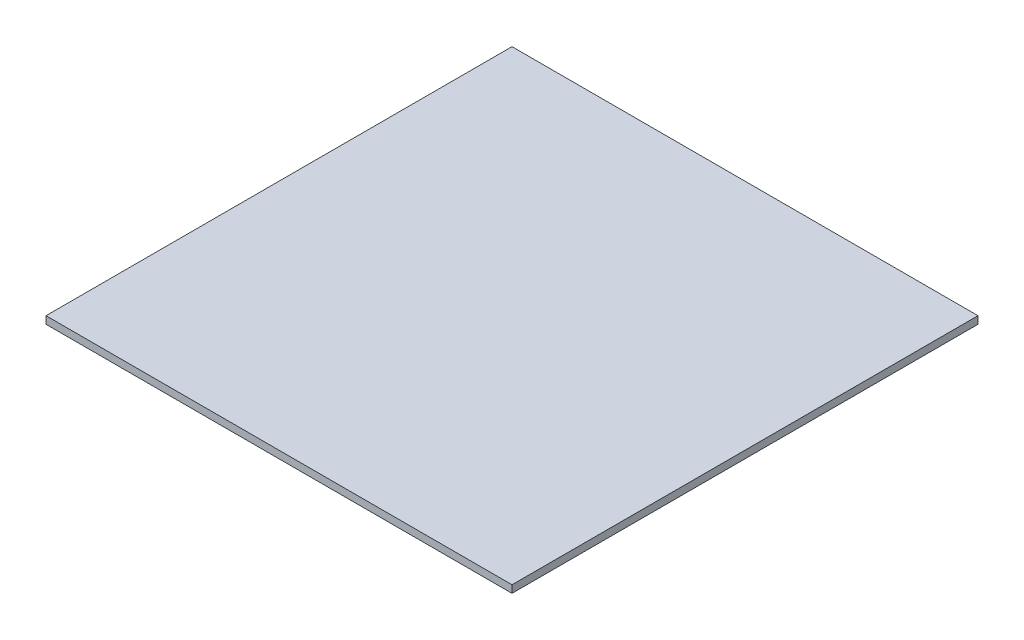
SolidWorks part; units mm, degrees
ref_plane "Front Plane" through (0, 0, 0) normal (0, 0, 1) x (1, 0, 0)
ref_plane "Top Plane" through (0, 0, 0) normal (0, 1, 0) x (1, 0, 0)
ref_plane "Right Plane" through (0, 0, 0) normal (1, 0, 0) x (0, 0, -1)
sketch "Sketch1" plane through (0, 0, 0) normal (0, 1, 0) x (1, 0, 0)
  line L1 (0, 0) -> (250, 0)
  line L2 (0, 0) -> (0, 250)
  line L3 (0, 250) -> (250, 250)
  line L4 (250, 0) -> (250, 250)
  dimension "D1" = 250
  dimension "D2" = 250
extrude "Boss-Extrude1" add sketch "Sketch1" along normal blind 4
equation "\"cf_tube_outer_diameter\" = 25mm"
equation "\"cf_tube_inner_diameter\" = 21mm"
equation "\"mid_plate_mid_to_top\" = 100mm"
equation "\"mid_plate_mid_to_bottom\" = 100mm"
equation "\"mid_plate_horizontal_spacing\" = 250mm"
equation "\"cf_plate_thickness\" = 4mm"
equation "\"mid_tube_length\" = 500mm"
equation "\"mid_plate_bottom_width\"= 150mm"
equation "\"D1@Sketch1\"=\"mid_plate_horizontal_spacing\""
equation "\"mid_support_plate_distance\" = 250mm"
equation "\"D2@Sketch1\"=\"mid_support_plate_distance\""
equation "\"D1@Boss-Extrude1\"=\"cf_plate_thickness\""
